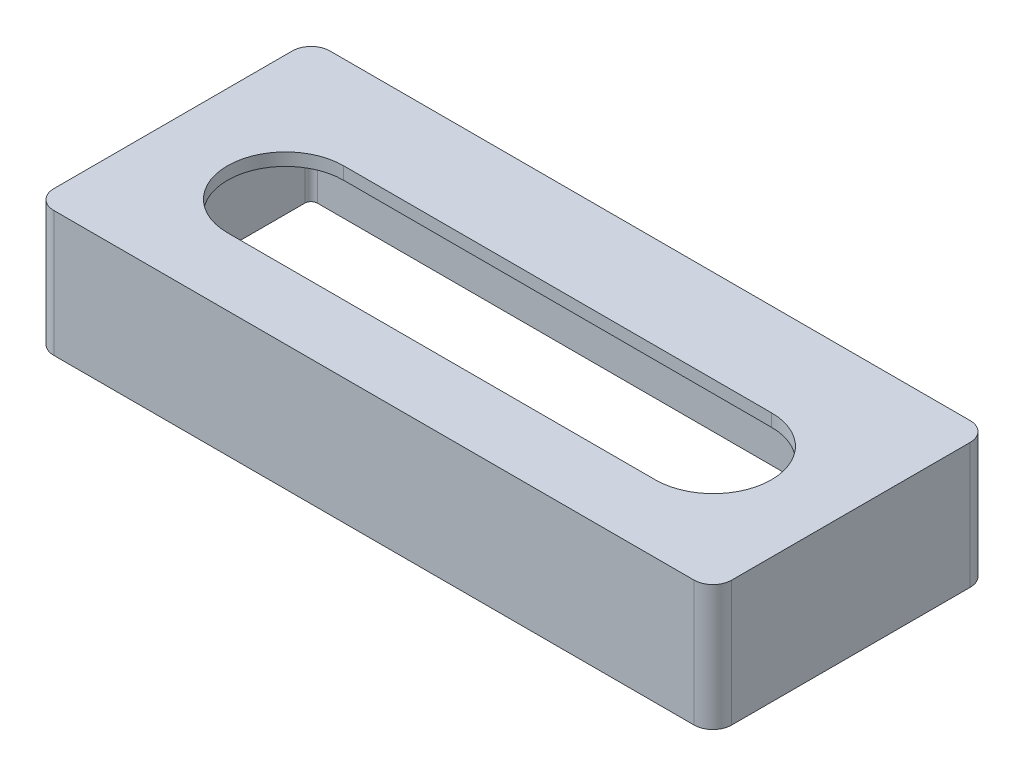
SolidWorks part; units mm, degrees
ref_plane "Front Plane" through (0, 0, 0) normal (0, 0, 1) x (1, 0, 0)
ref_plane "Top Plane" through (0, 0, 0) normal (0, 1, 0) x (1, 0, 0)
ref_plane "Right Plane" through (0, 0, 0) normal (1, 0, 0) x (0, 0, -1)
sketch "Sketch1" plane through (0, 0, 0) normal (0, 1, 0) x (1, 0, 0)
  line L0 (-34.075, 0) -> (34.075, 0) construction
  line L1 (-34.075, 9.25) -> (34.075, 9.25)
  line L2 (-34.075, -9.25) -> (34.075, -9.25)
  line L3 (0, 0) -> (0, 24) construction
  line L4 (0, 24) -> (-54, 24) construction
  line L6 (-51, 24) -> (51, 24)
  line L7 (-54, 21) -> (-54, -17)
  line L8 (-51, -20) -> (51, -20)
  line L9 (54, 21) -> (54, -17)
  arc A0 (-34.075, 9.25) -> (-34.075, -9.25) centre (-34.075, 0) ccw
  arc A1 (34.075, -9.25) -> (34.075, 9.25) centre (34.075, 0) ccw
  arc A2 (-54, -17) -> (-51, -20) centre (-51, -17) ccw
  arc A3 (51, -20) -> (54, -17) centre (51, -17) ccw
  arc A4 (51, 24) -> (54, 21) centre (51, 21) cw
  arc A5 (-51, 24) -> (-54, 21) centre (-51, 21) ccw
  point P2 (0, 0)
  point P19 (54, -20)
  point P22 (54, 24)
  dimension "D1" = 108
  dimension "D6" = 3
  dimension "D2" = 54
  dimension "D3" = 44
  dimension "D4" = 68.15
  dimension "D5" = 24
extrude "Boss-Extrude2" add sketch "Sketch1" against normal blind 20
shell "Shell1" thickness 2 removed face at (0, -20, 0)
sketch "Sketch2" plane through (0, -20, 0) normal (0, -1, 0) x (1, 0, 0)
  line L1 (49.6784, -16.8501) -> (-49.6784, -16.8501)
  line L2 (49.6784, -16.8501) -> (49.6784, 16.8501)
  line L3 (49.6784, 16.8501) -> (-49.6784, 16.8501)
  line L4 (-49.6784, -16.8501) -> (-49.6784, 16.8501)
  line L5 (49.6784, -16.8501) -> (-49.6784, 16.8501) construction
  line L6 (49.6784, 16.8501) -> (-49.6784, -16.8501) construction
  point P0 (0, 0)
extrude "Cut-Extrude1" cut sketch "Sketch2" against normal up to surface (18 mm away) up to face at (0, -2, 0)
sketch "Sketch3" plane through (0, 0, -24) normal (0, 0, -1) x (-1, 0, 0)
  line L0 (-51, -20) -> (51, -20) construction
  line L1 (-48.5847, -20) -> (-38.0582, -20)
  line L2 (-48.5847, -20) -> (-48.5847, -14.0227)
  line L3 (-48.5847, -14.0227) -> (-38.0582, -14.0227)
  line L4 (-38.0582, -20) -> (-38.0582, -14.0227)
extrude "Cut-Extrude2" cut sketch "Sketch3" against normal blind 2
